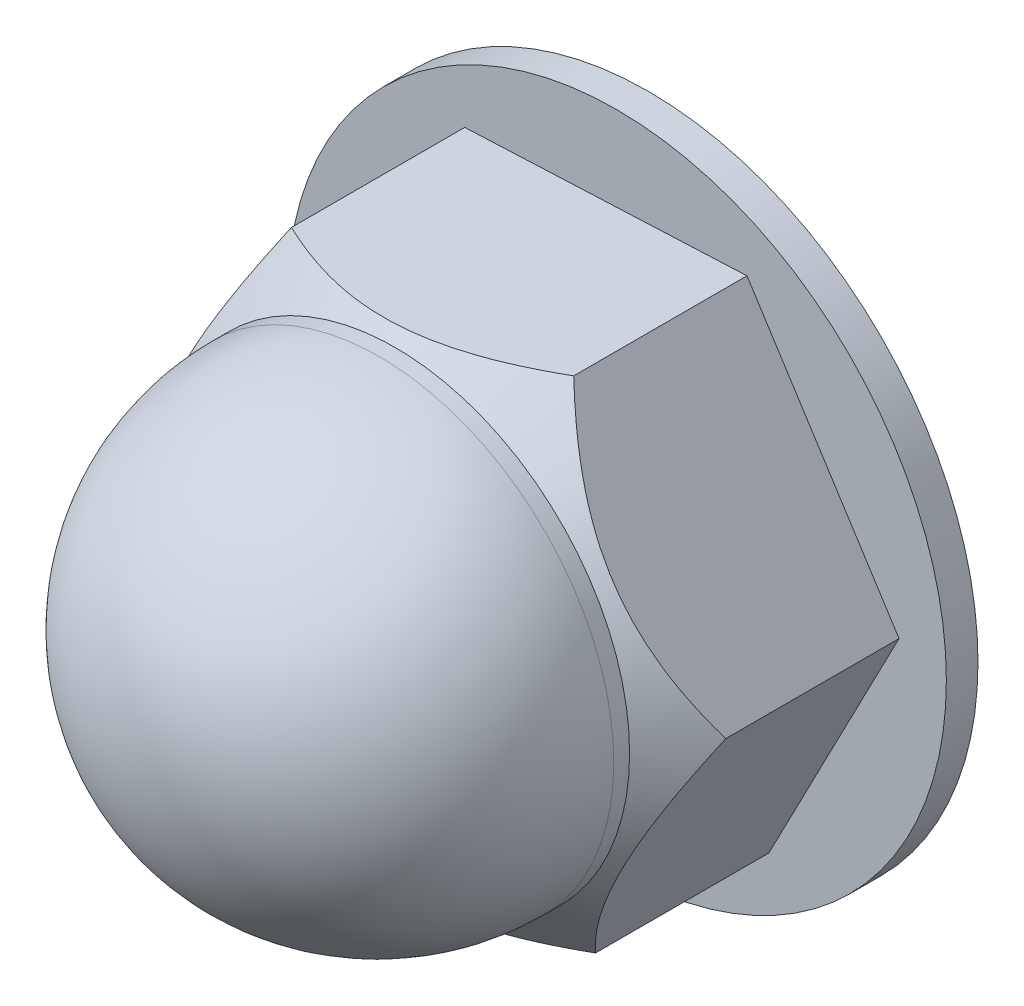
SolidWorks part; units mm, degrees
ref_plane "Front Plane" through (0, 0, 0) normal (0, 0, 1) x (1, 0, 0)
ref_plane "Top Plane" through (0, 0, 0) normal (0, 1, 0) x (1, 0, 0)
ref_plane "Right Plane" through (0, 0, 0) normal (1, 0, 0) x (0, 0, -1)
sketch "Sketch2" plane through (0, 0, 0) normal (0, 0, 1) x (1, 0, 0)
  circle A0 centre (74.4149, 117.3316) radius 20.8313
extrude "Boss-Extrude1" add sketch "Sketch2" along normal blind 2
sketch "Sketch3" plane through (0, 0, 2) normal (0, 0, 1) x (1, 0, 0)
  line L1 (82.6445, 133.1813) -> (64.8034, 132.3835)
  line L2 (64.8034, 132.3835) -> (56.5738, 116.5338)
  line L3 (56.5738, 116.5338) -> (66.1853, 101.4818)
  line L4 (66.1853, 101.4818) -> (84.0263, 102.2797)
  line L5 (84.0263, 102.2797) -> (92.2559, 118.1294)
  line L6 (92.2559, 118.1294) -> (82.6445, 133.1813)
  circle A0 centre (74.4149, 117.3316) radius 15.4663 construction
extrude "Boss-Extrude2" add sketch "Sketch3" along normal blind 14
sketch "Sketch4" plane through (0, 0, 16) normal (0, 0, 1) x (1, 0, 0)
  circle A0 centre (74.4149, 117.3316) radius 14.8109
  circle A1 centre (74.4149, 117.3316) radius 20.9161
extrude "Cut-Extrude1" cut sketch "Sketch4" against normal blind 14 draft 45
sketch "Sketch5" plane through (0, 0, 16) normal (0, 0, 1) x (1, 0, 0)
  circle A0 centre (74.4149, 117.3316) radius 14.8109
extrude "Boss-Extrude3" add sketch "Sketch5" along normal blind 1
dome "Dome1" faces to dome 1 distance 15 reverse direction no elliptical dome yes face at (89.2258, 117.3316, 17) parameters "D1"=15
